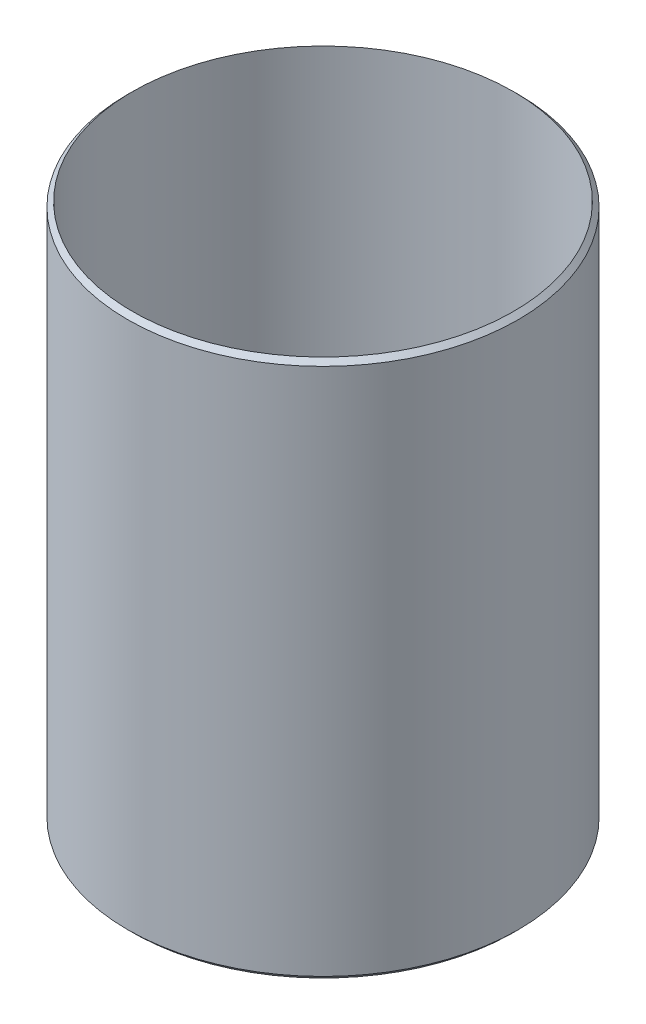
SolidWorks part; units mm, degrees
material "Plain Carbon Steel"
ref_plane "Front Plane" through (0, 0, 0) normal (0, 0, 1) x (1, 0, 0)
ref_plane "Top Plane" through (0, 0, 0) normal (0, 1, 0) x (1, 0, 0)
ref_plane "Right Plane" through (0, 0, 0) normal (1, 0, 0) x (0, 0, -1)
sketch "Sketch1" plane through (0, 0, 0) normal (0, 1, 0) x (1, 0, 0)
  circle A0 centre (0, 0) radius 80.55
  circle A1 centre (0, 0) radius 82.55
  dimension "D1" = 165.1
  dimension "D2" = 2
extrude "Boss-Extrude1" add sketch "Sketch1" along normal blind 227.4
chamfer "Chamfer1" distance 2 angle 45 2 edges at (0, 0, 82.55) (0, 227.4, 82.55)
equation "\"TubeDiameter\" = 6.500in"
equation "\"D1@Sketch1\"=\"TubeDiameter\""
